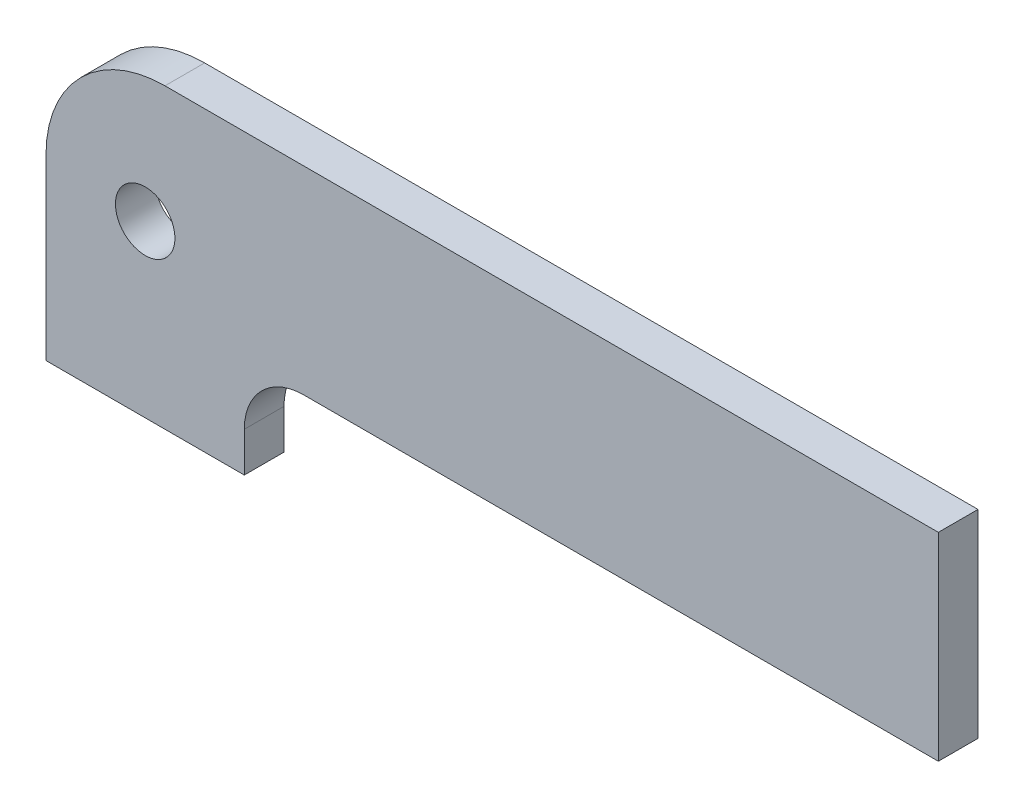
SolidWorks part; units mm, degrees
material "Thornel Mat VMA"
ref_plane "前视基准面" through (0, 0, 0) normal (0, 0, 1) x (1, 0, 0)
ref_plane "上视基准面" through (0, 0, 0) normal (0, 1, 0) x (1, 0, 0)
ref_plane "右视基准面" through (0, 0, 0) normal (1, 0, 0) x (0, 0, -1)
sketch "草图1" plane through (0, 0, 0) normal (0, 0, 1) x (1, 0, 0)
  line L0 (-17.5, -5) -> (-17.5, 5) construction
  line L1 (17.5, 5) -> (-17.5, 5)
  line L2 (17.5, 5) -> (17.5, -5)
  line L3 (17.5, -5) -> (-14.5, -5)
  line L5 (17.5, 5) -> (-17.5, -5) construction
  line L6 (17.5, -5) -> (-17.5, 5) construction
  line L7 (-17.5, 5) -> (-21.5, 5)
  line L8 (-17.5, -8) -> (-17.5, -10)
  line L9 (-17.5, -10) -> (-27.5, -10)
  line L10 (-27.5, -1) -> (-27.5, -10)
  arc A0 (-14.5, -5) -> (-17.5, -8) centre (-14.5, -8) ccw
  arc A1 (-21.5, 5) -> (-27.5, -1) centre (-21.5, -1) ccw
  point P0 (0, 0)
  dimension "D4" = 3
  dimension "D5" = 6
  dimension "D1" = 10
  dimension "D2" = 35
  dimension "D3" = 15
extrude "凸台-拉伸1" add sketch "草图1" along normal blind 2
hole_wizard "孔1" positions "草图2" profile "草图3" legacy end condition through all
sketch "草图2" plane through (0, 0, 2) normal (0, 0, 1) x (1, 0, 0)
  point P0 (-22.4984, -1.4104)
sketch "草图3" plane through (-22.4984, -1.4104, 2) normal (1, 0, 0) x (0, -1, 0)
  line L0 (0, 0) -> (0, 2)
  line L1 (0, 2) -> (1.5, 2)
  line L2 (1.5, 2) -> (1.5, 0)
  line L3 (1.5, 0) -> (0, 0)
  line L4 (0, 110) -> (0, -10) construction
  dimension "直径" = 3
  dimension "深度" = 2
